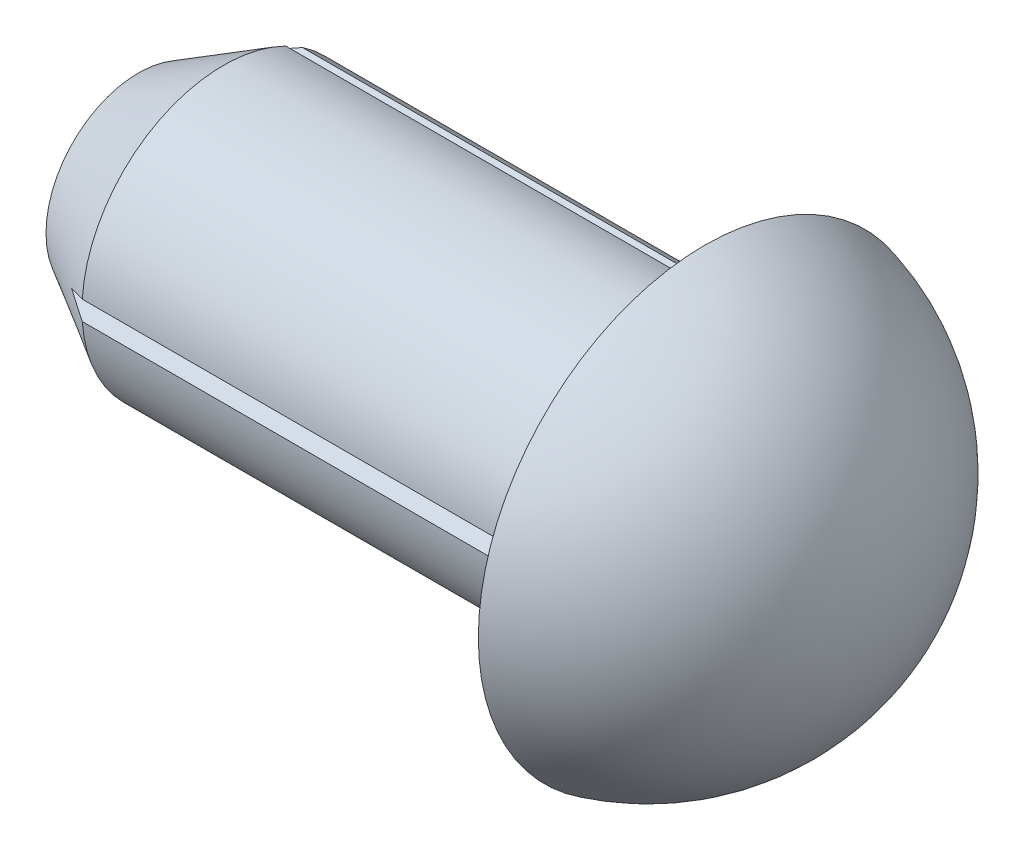
SolidWorks part; units mm, degrees
revolve "Base-Revolve" add sketch "Sketch1" angle 360 about L0
sketch "Sketch1" plane through (0, 0, 0) normal (0, 0, 1) x (1, 0, 0)
  line L0 (-40, 0) -> (40, 0) construction
  line L1 (-40, 0) -> (-40, 6.5359)
  line L2 (-34, 10) -> (0, 10)
  line L3 (0, 10) -> (0, 16)
  line L6 (12.4689, 0) -> (-40, 0)
  line L7 (-40, 6.5359) -> (-34, 10)
  arc A0 (12.4689, 0) -> (0, 16) centre (-4.0311, 0) ccw
  dimension "D1" = 30
  dimension "HeadRadius" = 16.5
  dimension "HeadDia" = 32
  dimension "Diameter" = 20
  dimension "Length" = 40
  dimension "ChamferLength" = 6
ref_plane "Plane1" through (0, 0, 0) normal (0, 0, 1) x (1, 0, 0)
ref_plane "Plane2" through (0, 0, 0) normal (0, 1, 0) x (1, 0, 0)
ref_plane "Plane3" through (0, 0, 0) normal (1, 0, 0) x (0, 0, -1)
sketch "Sketch2" plane through (-40, 0, 0) normal (-1, 0, 0) x (0, 0, 1)
  line L0 (0, 0) -> (12, 0) construction
  line L1 (9, 0) -> (10, 0.7002)
  line L2 (9, 0) -> (10, -0.7002)
  line L3 (10, -0.7002) -> (10, 0.7002)
  circle A0 centre (0, 0) radius 9 construction
  circle A1 centre (0, 0) radius 10 construction
  dimension "D1" = 18
  dimension "D2" = 70
  dimension "D3" = 35
extrude "Cut-Extrude1" cut sketch "Sketch2" against normal blind 37
pattern_circular "CirPattern1" count 3 over 360 about axis through (-40, 0, 0) along (1, 0, 0) of "Cut-Extrude1"
equation "\"D1@Sketch2\" = \"Diameter@Sketch1\" * .9"
equation "\"D3@Sketch2\" = \"D2@Sketch2\" / 2"
equation "\"D1@Cut-Extrude1\" = \"Length@Sketch1\" - \"ChamferLength@Sketch1\" / 2"
